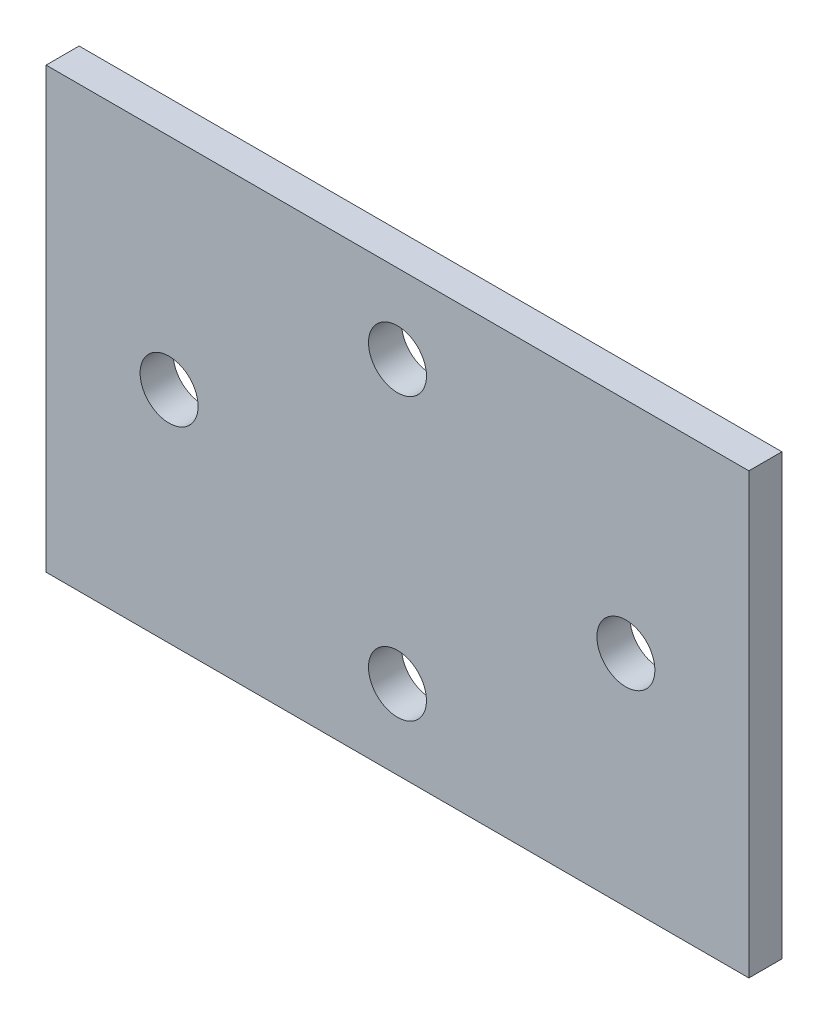
SolidWorks part; units mm, degrees
ref_plane "Front Plane" through (0, 0, 0) normal (0, 0, 1) x (1, 0, 0)
ref_plane "Top Plane" through (0, 0, 0) normal (0, 1, 0) x (1, 0, 0)
ref_plane "Right Plane" through (0, 0, 0) normal (1, 0, 0) x (0, 0, -1)
sketch "Sketch1" plane through (0, 0, 0) normal (0, 0, 1) x (1, 0, 0)
  line L0 (-50.8, -50.8) -> (50.8, -50.8) construction
  line L1 (-50.8, 50.8) -> (-50.8, -50.8) construction
  line L2 (50.8, -50.8) -> (50.8, -25.4) construction
  line L3 (-38.1, -34.8361) -> (-38.1, -41.3639) construction
  point P3 (0, -50.8)
  point P8 (-50.8, 0)
  point P9 (-38.1, -38.1)
  point P10 (50.8, -38.1)
  point P11 (0, 50.8)
  point P12 (-12.7, -38.1)
sketch "Sketch2" plane through (0, 0, 0) normal (1, 0, 0) x (0, 0, -1)
  line L0 (2.3876, 0) -> (-2.3876, 0) construction
  point P4 (0, 0)
  dimension "Thickness" = 4.7752
sketch "Sketch3" plane through (0, 0, 0) normal (0, 0, 1) x (1, 0, 0)
  line L0 (50.8, -25.4) -> (50.8, -50.8)
  line L1 (50.8, -50.8) -> (-50.8, -50.8)
  line L2 (-50.8, -50.8) -> (-50.8, 50.8)
  line L3 (-50.8, 50.8) -> (-25.4, 50.8)
  line L4 (-25.4, 50.8) -> (50.8, -25.4)
extrude "Boss-Extrude1" add sketch "Sketch3" against normal up to vertex (2.3876 mm away) and the other way up to vertex (2.3876 mm away) up to point (0, 0, -2.3876) other way up to point (0, 0, 2.3876)
sketch "Sketch4" plane through (0, 0, 2.3876) normal (0, 0, 1) x (1, 0, 0)
  line L0 (-38.1, -34.8361) -> (-38.1, -41.3639) construction
  line L1 (-50.8, -50.8) -> (0, 0) construction
  line L2 (-38.1, -38.1) -> (-12.7, -38.1) construction
  line L3 (-38.1, -38.1) -> (-38.1, -12.7) construction
  circle A0 centre (-38.1, -38.1) radius 3.2639
  circle A5 centre (-12.7, -38.1) radius 3.2639
  circle A6 centre (12.7, -38.1) radius 3.2639
  circle A7 centre (-38.1, -12.7) radius 3.2639
  circle A8 centre (-38.1, 12.7) radius 3.2639
  circle A9 centre (38.1, -38.1) radius 3.2639
  circle A10 centre (-38.1, 38.1) radius 3.2639
  dimension "D2" = 25.4
  dimension "D4" = 25.4
  dimension "D1" = 4
  dimension "D3" = 4
extrude "Cut-Extrude1" cut sketch "Sketch4" against normal through all
sketch "Sketch7" plane through (0, 0, 2.3876) normal (0, 0, 1) x (1, 0, 0)
  line L0 (50.8, -50.8) -> (50.8, -25.4) construction
  line L1 (-50.8, -50.8) -> (50.8, -50.8)
  line L2 (-50.8, -50.8) -> (-50.8, 50.8)
  line L3 (-50.8, 50.8) -> (50.8, 50.8)
  line L4 (50.8, -50.8) -> (50.8, 50.8)
  point P5 (0, 0)
  point P8 (-50.8, 50.8)
extrude "Boss-Extrude2" add sketch "Sketch7" against normal up to surface (4.7752 mm away) up to face at (-9.4361, -38.1, -2.3876)
sketch "Sketch9" plane through (0, 0, 2.3876) normal (0, 0, 1) x (1, 0, 0)
  line L0 (50.8, -50.8) -> (50.8, 50.8) construction
  line L1 (-50.8, -31.75) -> (50.8, -31.75)
  line L2 (-50.8, -31.75) -> (-50.8, 31.75)
  line L3 (-50.8, 31.75) -> (50.8, 31.75)
  line L4 (50.8, -31.75) -> (50.8, 31.75)
  line L5 (-50.8, -31.75) -> (50.8, 31.75) construction
  line L6 (-50.8, 31.75) -> (50.8, -31.75) construction
  point P0 (0, 0)
  dimension "D1" = 63.5
extrude "Cut-Extrude2" cut sketch "Sketch9" against normal through all flip side to cut contours L3 L4 L1 L2
sketch "Sketch10" plane through (0, 0, 2.3876) normal (0, 0, 1) x (1, 0, 0)
  line L0 (0, 0) -> (-80.2914, 0) construction
  circle A0 centre (-33.02, 0) radius 4.191
  circle A1 centre (33.02, 0) radius 4.191
  circle A2 centre (0, 20.32) radius 4.191
  circle A3 centre (0, -20.32) radius 4.191
  dimension "D1" = 8.382
  dimension "D4" = 8.382
  dimension "D2" = 33.02
  dimension "D3" = 33.02
  dimension "D5" = 20.32
extrude "Cut-Extrude3" cut sketch "Sketch10" against normal through all
equation "\"D2@Sketch4\"=\"Hole Spacing@Sketch1\""
equation "\"D1@Sketch4\"=\"#Holes@Sketch1\""
equation "\"D4@Sketch4\"=\"Hole Spacing@Sketch1\""
equation "\"D3@Sketch4\"=\"#Holes@Sketch1\""
equation "\"D3@Sketch10\"=\"D2@Sketch10\""
